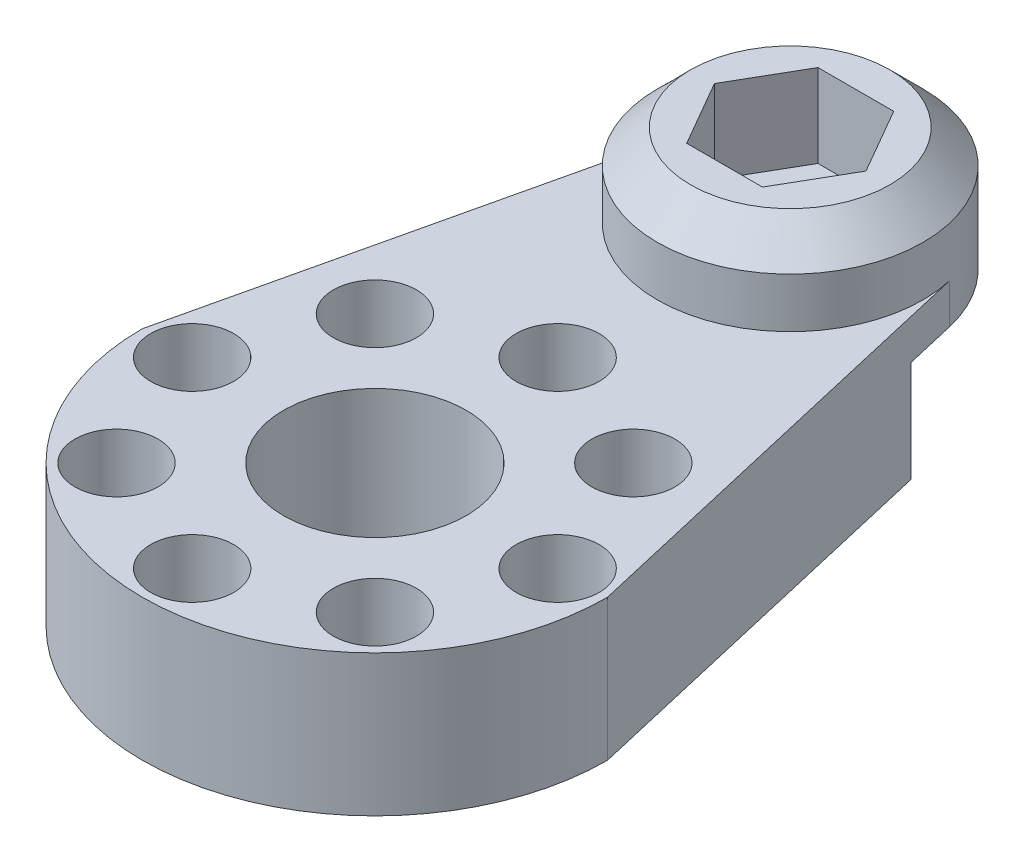
SolidWorks part; units mm, degrees
material "3003 Alloy"
ref_plane "Front Plane" through (0, 0, 0) normal (0, 0, 1) x (1, 0, 0)
ref_plane "Top Plane" through (0, 0, 0) normal (0, 1, 0) x (1, 0, 0)
ref_plane "Right Plane" through (0, 0, 0) normal (1, 0, 0) x (0, 0, -1)
sketch "Sketch1" plane through (0, 0, 0) normal (0, 1, 0) x (1, 0, 0)
  line L0 (0, 0) -> (0, 25) construction
  line L1 (-14, 0) -> (-14, 25)
  line L2 (14, 0) -> (14, 25)
  arc A0 (-14, 0) -> (14, 0) centre (0, 0) ccw
  arc A1 (14, 25) -> (-14, 25) centre (0, 25) ccw
  circle A2 centre (0, 25) radius 2
  circle A3 centre (0, 0) radius 5.5
  point P3 (0, 12.5)
  dimension "D3" = 11
  dimension "D4" = 4
  dimension "D1" = 25
  dimension "D2" = 28
extrude "Boss-Extrude1" add sketch "Sketch1" along normal blind 8.5
sketch "Sketch2" plane through (0, 8.5, 0) normal (0, 1, 0) x (1, 0, 0)
  line L0 (0, 0) -> (0, 11) construction
  circle A0 centre (0, 11) radius 1.55
  circle A1 centre (7.7782, 7.7782) radius 1.55
  circle A2 centre (11, 0) radius 1.55
  circle A3 centre (7.7782, -7.7782) radius 1.55
  circle A4 centre (0, -11) radius 1.55
  circle A5 centre (-7.7782, -7.7782) radius 1.55
  circle A6 centre (-11, 0) radius 1.55
  circle A7 centre (-7.7782, 7.7782) radius 1.55
  circle A8 centre (0, 0) radius 11 construction
  point P21 (0, 0)
  dimension "D1" = 3.1
  dimension "D2" = 11
  dimension "D3" = 8
extrude "Cut-Extrude1" cut sketch "Sketch2" against normal through all
sketch "Sketch3" plane through (0, 8.5, 0) normal (0, 1, 0) x (1, 0, 0)
  line L0 (-14, 0) -> (-7.7938, 26.8045)
  line L1 (14, 0) -> (7.7938, 26.8045)
  line L2 (-14, 25) -> (-14, 0) construction
  line L3 (14, 0) -> (14, 25) construction
  line L4 (-14, 25) -> (-14, 0)
  line L5 (14, 0) -> (14, 25)
  arc A1 (14, 25) -> (-14, 25) centre (0, 25) ccw construction
  circle A3 centre (0, 25) radius 8
  arc A4 (14, 25) -> (-14, 25) centre (0, 25) ccw
  line M12 (14, 0) -> (14, 25)
  arc M13 (14, 25) -> (-14, 25) centre (0, 25) ccw
  line M14 (-14, 25) -> (-14, 0)
  dimension "D1" = 16
extrude "Cut-Extrude2" cut sketch "Sketch3" against normal through all contours A3 L1 L0 M12 M13 M14 region at (-13.5199, 8.5, -12.5)
sketch "Croquis1" plane through (0, 8.5, 0) normal (0, 1, 0) x (1, 0, 0)
  line L1 (4.5611, 25) -> (2.2805, 28.95)
  line L2 (2.2805, 28.95) -> (-2.2805, 28.95)
  line L3 (-2.2805, 28.95) -> (-4.5611, 25)
  line L4 (-4.5611, 25) -> (-2.2805, 21.05)
  line L5 (-2.2805, 21.05) -> (2.2805, 21.05)
  line L6 (2.2805, 21.05) -> (4.5611, 25)
  circle A0 centre (0, 25) radius 3.95 construction
  circle A1 centre (0, 25) radius 8
  dimension "D1" = 7.9
extrude "Saliente-Extruir1" add sketch "Croquis1" along normal blind 5
chamfer "Chaflán1" distance 2 angle 45 1 edges at (0, 13.5, -17)
sketch "Croquis2" plane through (0, 0, 0) normal (0, -1, 0) x (-1, 0, 0)
  line L0 (-7.7938, 26.8045) -> (-10.0639, 17)
  line L1 (-14, 0) -> (-7.7938, 26.8045) construction
  line L2 (-10.0639, 17) -> (10.0639, 17)
  line L3 (14, 0) -> (7.7938, 26.8045) construction
  line L4 (10.0639, 17) -> (7.7938, 26.8045)
  arc A1 (-7.7938, 26.8045) -> (7.7938, 26.8045) centre (0, 25) cw
extrude "Cortar-Extruir1" cut sketch "Croquis2" against normal blind 6.1
sketch "Croquis3" plane through (-13.2877, 0, -3.0766) normal (-0.9742, 0, -0.2256) x (-0.2256, 0, 0.9742)
  line L0 (-14.2918, 6.1) -> (-24.3557, 6.1) construction
  line L1 (-14.2918, 6.1) -> (-14.2918, 0) construction
  line L3 (-19.3237, 7.4101) -> (-13.6045, 7.4101)
  line L4 (-13.6045, 7.4101) -> (-13.6045, 3.05)
  line L5 (-13.6045, 3.05) -> (-14.2918, 3.05)
  line L6 (-19.3237, 6.1) -> (-19.3237, 7.4101)
  arc A0 (-19.3237, 6.1) -> (-14.2918, 3.05) centre (-17.7097, 3.087) cw
extrude "Saliente-Extruir2" add sketch "Croquis3" along direction (-1, 0, 0) on the side against the normal up to surface (17.8577 mm away) up to face at (10.6192, 4.8667, -14.6015)
sketch "Croquis4" plane through (0, 8.5, 0) normal (0, 1, 0) x (1, 0, 0)
  circle A0 centre (0, 11) radius 2.5
  dimension "D1" = 5
extrude "Cortar-Extruir2" cut sketch "Croquis4" against normal blind 6
pattern_circular "MatrizC1" count 8 over 360 about axis through (0, 8.5, 0) along (0, 1, 0) of "Cortar-Extruir2"
sketch "Croquis5" plane through (0, 6.1, 0) normal (0, -1, 0) x (1, 0, 0)
  line L2 (7.7938, -26.8045) -> (9.657, -18.7573) construction
  line L8 (9.657, -16.5742) -> (0, -16.5742)
  line L10 (14, 0) -> (7.7938, -26.8045) construction
  line L12 (9.657, -16.5742) -> (10.1625, -16.5742)
  line L13 (8.4994, -23.7573) -> (10.1625, -16.5742)
  line L15 (8.4994, -23.7573) -> (0, -16.5742)
extrude "Saliente-Extruir3" add sketch "Croquis5" along normal up to surface (6.1 mm away) up to face at (-7.7782, 0, -6.2282)
